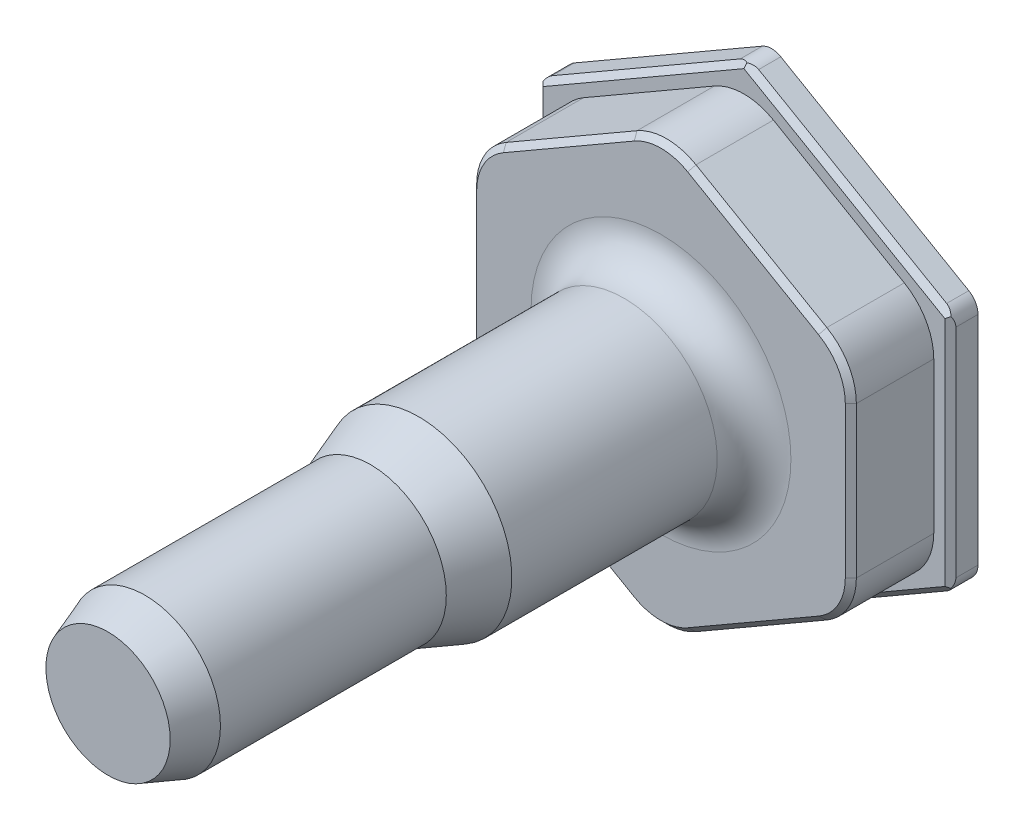
SolidWorks part; units mm, degrees
ref_plane "Front Plane" through (0, 0, 0) normal (0, 0, 1) x (1, 0, 0)
ref_plane "Top Plane" through (0, 0, 0) normal (0, 1, 0) x (1, 0, 0)
ref_plane "Right Plane" through (0, 0, 0) normal (1, 0, 0) x (0, 0, -1)
sketch "Sketch1" plane through (0, 0, 0) normal (0, 0, 1) x (1, 0, 0)
  line L12 (0, 11.8934) -> (10.3, 5.9467)
  line L14 (10.3, 5.9467) -> (10.3, -5.9467)
  line L15 (10.3, -5.9467) -> (0, -11.8934)
  line L16 (0, -11.8934) -> (-10.3, -5.9467)
  line L17 (-10.3, -5.9467) -> (-10.3, 5.9467)
  line L18 (-10.3, 5.9467) -> (0, 11.8934)
  line L19 (-11.2, 6.4663) -> (0, 12.9326)
  line L20 (0, 12.9326) -> (11.2, 6.4663)
  line L21 (11.2, 6.4663) -> (11.2, -6.4663)
  line L22 (11.2, -6.4663) -> (0, -12.9326)
  line L23 (0, -12.9326) -> (-11.2, -6.4663)
  line L24 (-11.2, -6.4663) -> (-11.2, 6.4663)
  circle A1 centre (0, 0) radius 3.25
  circle A2 centre (0, 0) radius 5.05
  circle A3 centre (0, 0) radius 2.125
  circle A4 centre (0, 0) radius 4.1
  point P3 (0, 11.8934)
  point P4 (10.3, 5.9467)
  point P7 (10.3, -5.9467)
  point P9 (0, -11.8934)
  point P10 (-10.3, -5.9467)
  point P12 (-10.3, 5.9467)
  point P13 (0, 0)
  dimension "D1" = 20.6
  dimension "D6" = 6.5
  dimension "D7" = 10.1
  dimension "D8" = 4.25
  dimension "D9" = 8.2
  dimension "D2" = 6
  dimension "D3" = 120
  dimension "D4" = 120
  dimension "D5" = 0.9
extrude "Boss-Extrude1" add sketch "Sketch1" along normal blind 1.5 contours L19 L20 L21 L22 L23 L24
ref_plane "Plane1" through (-11.2, -6.4663, 0) normal (-0.866, 0.5, 0) x (0, 0, 1)
ref_plane "Plane2" through (0, -12.9326, 0) normal (-0.866, 0.5, 0) x (0, 0, 1)
extrude "Boss-Extrude3" add sketch "Sketch1<8>" along normal blind 36 contours A4
sketch "Sketch1<8>" plane through (0, 0, 0) normal (0, 0, 1) x (1, 0, 0) same geometry as "Sketch1"
extrude "Boss-Extrude4" add sketch "Sketch1<9>" along normal blind 19 contours A2
sketch "Sketch1<9>" plane through (0, 0, 0) normal (0, 0, 1) x (1, 0, 0) same geometry as "Sketch1"
shell "Shell1" thickness 2
extrude "Cut-Extrude1" cut sketch "Sketch1<10>" along normal blind 17 contours A1
sketch "Sketch1<10>" plane through (0, 0, 0) normal (0, 0, 1) x (1, 0, 0) same geometry as "Sketch1"
extrude "Boss-Extrude2" add sketch "Sketch1<3>" along normal blind 6 contours L17 L18 L12 L14 L15 L16 | A1
sketch "Sketch1<3>" plane through (0, 0, 0) normal (0, 0, 1) x (1, 0, 0) same geometry as "Sketch1"
chamfer "Chamfer1" distance 2 angle 20 1 edges at (4.1, 0, 36) first distance on face at (4.1, 0, 19)
chamfer "Chamfer2" distance 1 angle 70 1 edges at (4.1, 0, 19) first distance on face at (4.1, 0, 19)
chamfer "Chamfer3" distance 0.7 angle 60 1 edges at (2.1, 0, 17) first distance on face at (2.1, 0, 17)
chamfer "Chamfer6" distance 0.3 angle 45 1 edges at (3.25, 0, 0)
ref_plane "Plane3" through (0, 0, 5) normal (0, 0, 1) x (1, 0, 0)
sketch "Sketch2" plane through (0, 0, 5) normal (0, 0, 1) x (1, 0, 0)
  line L1 (-17.7118, 13.112) -> (21.871, 13.112)
  line L2 (-17.7118, 13.112) -> (-17.7118, -17.4474)
  line L3 (-17.7118, -17.4474) -> (21.871, -17.4474)
  line L4 (21.871, 13.112) -> (21.871, -17.4474)
fillet "Fillet1" radius 3.2 6 edges at (10.3, -5.9467, 3.75) (0, -11.8934, 3.75) (-10.3, -5.9467, 3.75) (-10.3, 5.9467, 3.75) (0, 11.8934, 3.75) (10.3, 5.9467, 3.75)
chamfer "Chamfer5" distance 0.3 angle 45 18 edges at (-10.3, 0, 6) (-5.15, 8.9201, 6) (5.15, 8.9201, 6) (10.3, 0, 6) (5.15, -8.9201, 6) (-5.15, -8.9201, 6) (11.2, 0, 1.5) (5.6, -9.6995, 1.5) (-5.6, -9.6995, 1.5) (-11.2, 0, 1.5) (5.6, 9.6995, 1.5) (-5.6, 9.6995, 1.5) (0, -11.3984, 6) (-9.8713, -5.6992, 6) (-9.8713, 5.6992, 6) (0, 11.3984, 6) (9.8713, 5.6992, 6) (9.8713, -5.6992, 6)
fillet "Fillet2" radius 1 6 edges at (11.2, -6.4663, 0.6) (11.2, 6.4663, 0.6) (0, 12.9326, 0.6) (0, -12.9326, 0.6) (-11.2, -6.4663, 0.6) (-11.2, 6.4663, 0.6)
fillet "Fillet3" radius 2 1 edges at (-5.05, 0, 6)
